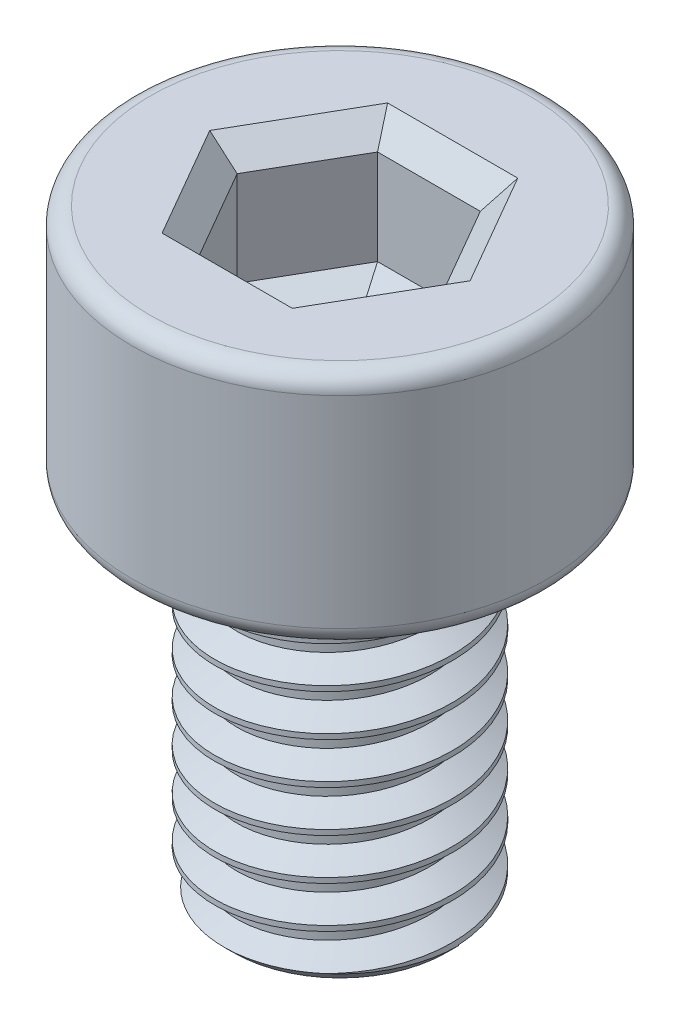
SolidWorks part; units mm, degrees
material "AISI 1020"
ref_plane "Front Plane" through (0, 0, 0) normal (0, 0, 1) x (1, 0, 0)
ref_plane "Top Plane" through (0, 0, 0) normal (0, 1, 0) x (1, 0, 0)
ref_plane "Right Plane" through (0, 0, 0) normal (1, 0, 0) x (0, 0, -1)
sketch "Sketch1" plane through (0, 0, 0) normal (0, 1, 0) x (1, 0, 0)
  circle A0 centre (0, 0) radius 3.5
  dimension "D1" = 7
extrude "Boss-Extrude1" add sketch "Sketch1" along normal blind 4
sketch "Sketch2" plane through (0, 4, 0) normal (0, 1, 0) x (1, 0, 0)
  line L1 (1.7321, 0) -> (0.866, 1.5)
  line L2 (0.866, 1.5) -> (-0.866, 1.5)
  line L3 (-0.866, 1.5) -> (-1.7321, 0)
  line L4 (-1.7321, 0) -> (-0.866, -1.5)
  line L5 (-0.866, -1.5) -> (0.866, -1.5)
  line L6 (0.866, -1.5) -> (1.7321, 0)
  circle A0 centre (0, 0) radius 1.5 construction
  dimension "D1" = 3
extrude "Cut-Extrude1" cut sketch "Sketch2" against normal blind 2
sketch "Sketch5" plane through (0, 2, 0) normal (0, 1, 0) x (1, 0, 0)
  line L6 (0.866, -1.5) -> (1.7321, 0)
  line L7 (1.7321, 0) -> (0.866, 1.5)
  line L8 (0.866, 1.5) -> (-0.866, 1.5)
  line L9 (-0.866, 1.5) -> (-1.7321, 0)
  line L10 (-1.7321, 0) -> (-0.866, -1.5)
  line L11 (-0.866, -1.5) -> (0.866, -1.5)
  line L12 (0.866, -1.5) -> (1.7321, 0)
  line L13 (1.7321, 0) -> (0.866, 1.5)
  line L14 (0.866, 1.5) -> (-0.866, 1.5)
  line L15 (-0.866, 1.5) -> (-1.7321, 0)
  line L16 (-1.7321, 0) -> (-0.866, -1.5)
  line L17 (-0.866, -1.5) -> (0.866, -1.5)
  dimension "D1" = 0
extrude "Cut-Extrude2" cut sketch "Sketch5" against normal blind 1 draft 70
sketch "Sketch6" plane through (0, 0, 0) normal (0, -1, 0) x (1, 0, 0)
  circle A0 centre (0, 0) radius 2
  dimension "D1" = 4
extrude "Boss-Extrude2" add sketch "Sketch6" along normal blind 6
chamfer "Chamfer1" distance 0.4 angle 45 6 edges at (0, 4, 1.5) (-1.299, 4, 0.75) (-1.299, 4, -0.75) (0, 4, -1.5) (1.299, 4, -0.75) (1.299, 4, 0.75)
fillet "Fillet1" radius 0.3 2 edges at (0, 0, 3.5) (0, 4, 3.5)
fillet "Fillet2" radius 0.15 1 edges at (0, 0, -2)
thread "Thread1" pitch 0.7 start angle 0, offset 0.4, length 0, pitch 0.7, diameter 4
ref_plane "Plane1" through (2, -6.4, 0) normal (0, 0, 1) x (1, 0, 0)
sketch "Thread Profile1" plane through (2, -6.4, 0) normal (0, 0, 1) x (1, 0, 0)
  line L0 (0, 0) -> (0, 0.7) construction
  line L11 (0, 0) -> (0, 0.6125)
  line L12 (0, 0.6125) -> (-0.3789, 0.3937)
  line L13 (-0.3789, 0.3937) -> (-0.3789, 0.2187)
  line L15 (-0.3789, 0.2187) -> (0, 0)
  line L17 (-0.3789, 0.3062) -> (0, 0.3062) construction
  point P2 (0, 0)
  dimension "Pitch" = 0.7
  dimension "Profile_Angle" = 60
  dimension "Profile_Land" = 0.175
  dimension "Profile_Height" = 0.3789
chamfer "Chamfer2" distance 0.2 angle 45 1 edges
